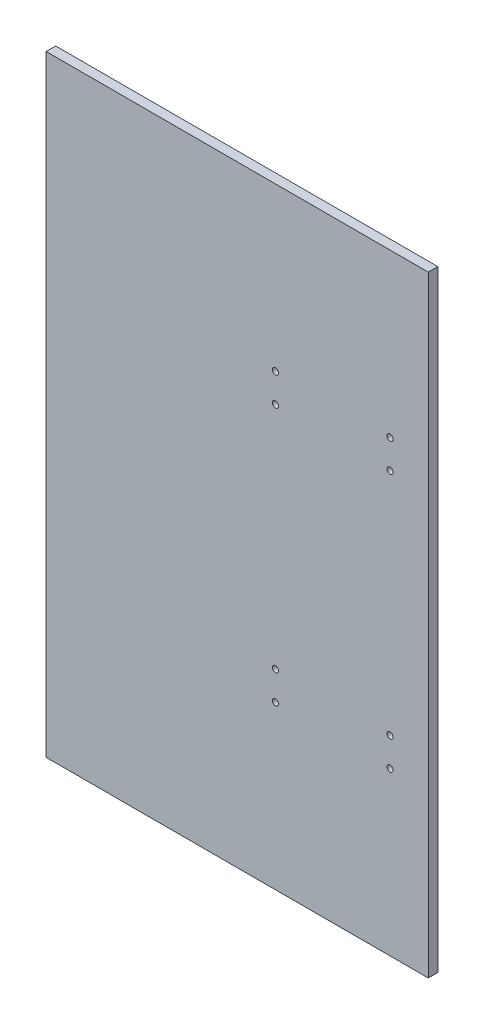
SolidWorks part; units mm, degrees
ref_plane "Front Plane" through (0, 0, 0) normal (0, 0, 1) x (1, 0, 0)
ref_plane "Top Plane" through (0, 0, 0) normal (0, 1, 0) x (1, 0, 0)
ref_plane "Right Plane" through (0, 0, 0) normal (1, 0, 0) x (0, 0, -1)
sketch "Sketch1" plane through (0, 0, 0) normal (0, 0, 1) x (1, 0, 0)
  line L1 (-100, -160) -> (100, -160)
  line L2 (-100, -160) -> (-100, 160)
  line L3 (-100, 160) -> (100, 160)
  line L4 (100, -160) -> (100, 160)
  line L5 (-100, -160) -> (100, 160) construction
  line L6 (-100, 160) -> (100, -160) construction
  point P0 (0, 0)
  dimension "D1" = 320
  dimension "D2" = 200
extrude "Boss-Extrude1" add sketch "Sketch1" along normal blind 5
sketch "Sketch2" plane through (0, 0, 0) normal (0, 0, -1) x (-1, 0, 0)
  line L0 (-95, 0) -> (-80, 0) construction
  line L1 (-95, 160) -> (-95, -160) construction
  line L2 (-80, 0) -> (-80, 60) construction
  line L3 (-80, 60) -> (-80, 75) construction
  line L4 (-80, 0) -> (-50, 0) construction
  line L5 (-50, 0) -> (-50, 25.4966) construction
  circle A0 centre (-80, 75) radius 1.6
  circle A1 centre (-80, 60) radius 1.6
  circle A2 centre (-80, -60) radius 1.6
  circle A3 centre (-80, -75) radius 1.6
  circle A4 centre (-20, -75) radius 1.6
  circle A5 centre (-20, -60) radius 1.6
  circle A6 centre (-20, 60) radius 1.6
  circle A7 centre (-20, 75) radius 1.6
  dimension "D5" = 3.2
  dimension "D6" = 3.2
  dimension "D1" = 15
  dimension "D2" = 60
  dimension "D3" = 15
  dimension "D4" = 30
extrude "Cut-Extrude1" cut sketch "Sketch2" against normal up to next
